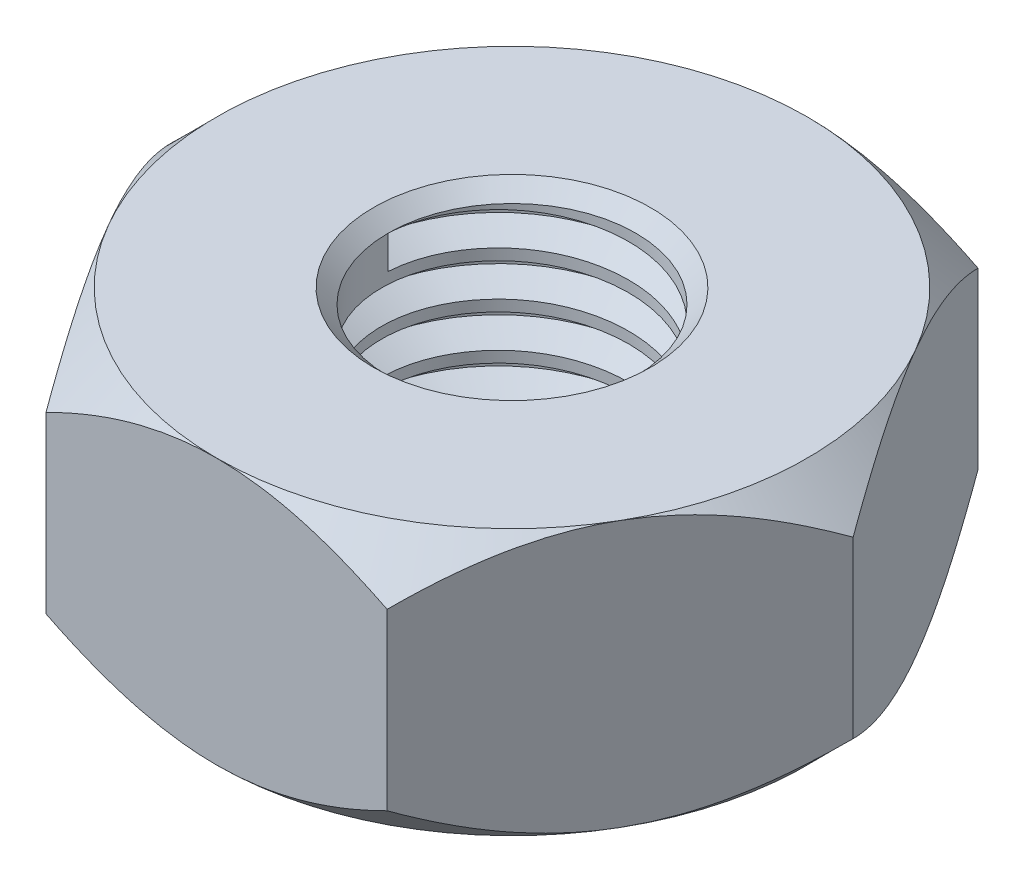
SolidWorks part; units mm, degrees
ref_plane "Front Plane" through (0, 0, 0) normal (0, 0, 1) x (1, 0, 0)
ref_plane "Top Plane" through (0, 0, 0) normal (0, 1, 0) x (1, 0, 0)
ref_plane "Right Plane" through (0, 0, 0) normal (1, 0, 0) x (0, 0, -1)
sketch "Sketch1" plane through (0, 0, 0) normal (0, 1, 0) x (1, 0, 0)
  line L1 (5.7735, -10) -> (11.547, 0)
  line L2 (11.547, 0) -> (5.7735, 10)
  line L3 (5.7735, 10) -> (-5.7735, 10)
  line L4 (-5.7735, 10) -> (-11.547, 0)
  line L5 (-11.547, 0) -> (-5.7735, -10)
  line L6 (-5.7735, -10) -> (5.7735, -10)
  circle A0 centre (0, 0) radius 10 construction
  dimension "D1" = 20
extrude "Boss-Extrude1" add sketch "Sketch1" along normal mid plane 9
sketch "Sketch2" plane through (0, 4.5, 0) normal (0, 1, 0) x (1, 0, 0)
  circle A0 centre (0, 0) radius 4.19
  dimension "D1" = 8.38
extrude "Cut-Extrude1" cut sketch "Sketch2" against normal through all
chamfer "Chamfer1" distance 0.5 angle 45 2 edges at (0, -4.5, 4.19) (0, 4.5, 4.19)
thread "Thread2" pitch 1.5 method cut profile "Thread Profile2" start angle 0, offset 0.0001, length 0, pitch 1.5, diameter 8.38
ref_plane "Plane2" through (-4.19, 4.0001, 0) normal (0, 0, 1) x (-1, 0, 0)
sketch "Thread Profile2" plane through (-4.19, 4.0001, 0) normal (0, 0, 1) x (-1, 0, 0)
  line L0 (0, 0) -> (0, 1.5) construction
  line L1 (0, 0) -> (0.8119, 0.4687)
  line L2 (0.8119, 0.4687) -> (0.8119, 0.6562)
  line L3 (0.8119, 0.6562) -> (0, 1.125)
  line L4 (0.8119, 0.5625) -> (0, 0.5625) construction
  line L11 (0, 0) -> (0, 1.125)
  point P2 (0, 0)
  dimension "Pitch" = 1.5
  dimension "Profile_Angle" = 60
  dimension "Profile_Land" = 0.1875
  dimension "Profile_Height" = 0.8119
sketch "Sketch11" plane through (0, 4.5, 0) normal (0, 1, 0) x (1, 0, 0)
  circle A0 centre (0, 0) radius 10
extrude "Cut-Extrude5" cut sketch "Sketch11" against normal blind 10 draft 45 flip side to cut
mirror "Mirror4" about plane through (0, 0, 0) normal (0, 1, 0) of "Cut-Extrude5"
